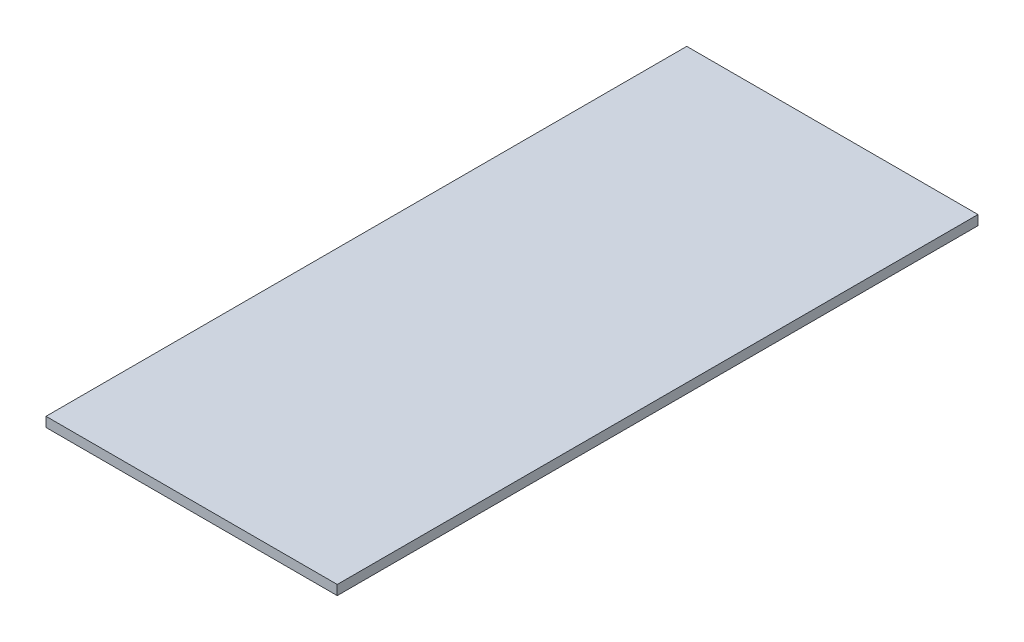
SolidWorks part; units mm, degrees
material "Plain Carbon Steel"
ref_plane "Front Plane" through (0, 0, 0) normal (0, 0, 1) x (1, 0, 0)
ref_plane "Top Plane" through (0, 0, 0) normal (0, 1, 0) x (1, 0, 0)
ref_plane "Right Plane" through (0, 0, 0) normal (1, 0, 0) x (0, 0, -1)
sketch "Sketch1" plane through (0, 29.1433, 0) normal (0, -1, 0) x (1, 0, 0)
  line L1 (-30.3006, 478.4331) -> (-330.3006, 478.4331)
  line L2 (-30.3006, 478.4331) -> (-30.3006, -181.5669)
  line L3 (-30.3006, -181.5669) -> (-330.3006, -181.5669)
  line L4 (-330.3006, 478.4331) -> (-330.3006, -181.5669)
extrude "Boss-Extrude1" add sketch "Sketch1" along normal blind 10
sketch "Centerlines" plane through (0, 29.1433, 0) normal (0, 1, 0) x (1, 0, 0)
  line L0 (-180.3006, 181.5669) -> (-180.3006, -478.4331) construction
  line L1 (-330.3006, 181.5669) -> (-30.3006, 181.5669) construction
  line L2 (-30.3006, -478.4331) -> (-330.3006, -478.4331) construction
  line L3 (-30.3006, -148.4331) -> (-330.3006, -148.4331) construction
  line L4 (-30.3006, 181.5669) -> (-30.3006, -478.4331) construction
  line L5 (-330.3006, -478.4331) -> (-330.3006, 181.5669) construction
  point P12 (-180.3006, -148.4331)
